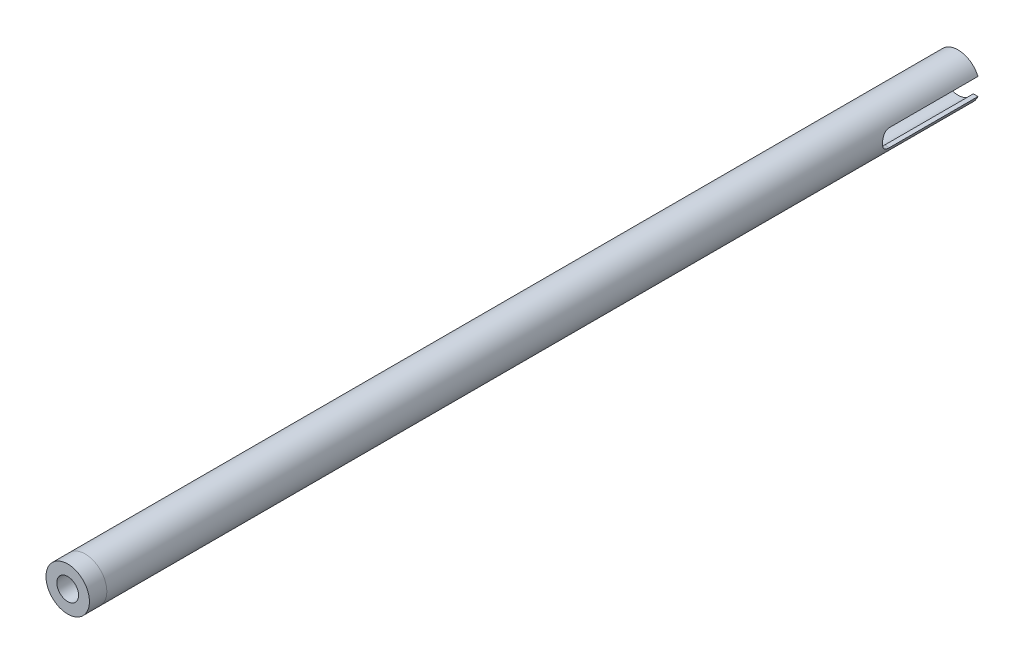
SolidWorks part; units mm, degrees
ref_plane "Front Plane" through (0, 0, 0) normal (0, 0, 1) x (1, 0, 0)
ref_plane "Top Plane" through (0, 0, 0) normal (0, 1, 0) x (1, 0, 0)
ref_plane "Right Plane" through (0, 0, 0) normal (1, 0, 0) x (0, 0, -1)
sketch "Axis" plane through (0, 0, 0) normal (0, 1, 0) x (1, 0, 0)
  line L0 (0, 0) -> (0, 325.114) construction
  line L1 (0, 0) -> (0, -34.925) construction
  line L2 (0, 325.114) -> (-7.9375, 325.114) construction
  line L4 (0, 354.4828) -> (-10.3187, 316.3034) construction
  dimension "D1" = 34.925
  dimension "D2" = 7.9375
sketch "Sketch1" plane through (0, 0, 0) normal (0, 0, 1) x (1, 0, 0)
  line L0 (-7.9375, 0) -> (7.9375, 0) construction
  line L1 (-7.2748, 3.175) -> (7.2748, 3.175)
  line L2 (-7.2748, -3.175) -> (7.2748, -3.175)
  circle A0 centre (0, 0) radius 7.9375
  circle A1 centre (0, 0) radius 6.4135
  circle A2 centre (0, 0) radius 3.9688
  dimension "D1" = 15.875
  dimension "D3" = 7.9375
  dimension "D2" = 1.524
  dimension "D4" = 6.35
extrude "Threaded insert 1-1" add sketch "Sketch1" against normal blind 6.35 contours A2 L1 A1 | A1 L1 A0 | A2 L0 A1 L1 | A1 L0 A0 L1 | L0 A1 L2 A0 | L0 A2 L2 A1 | A2 L2 A1 | A1 L2 A0 | L0 A1 L2 A2 | L0 A0 L2 A1 | A0 L0 A1 L1 | A1 L0 A2 L1 region at (4.7887, 1.6543, 0) region at (4.7887, -1.6543, 0) region at (6.9234, 1.6163, 0) region at (6.9234, -1.6163, 0) region at (-4.7887, -1.6543, 0) region at (-4.7887, 1.6543, 0) region at (0, 4.6159, 0) region at (0, -4.6159, 0) region at (0, 6.5666, 0) region at (6.4237, -3.3281, 0) region at (-6.9234, -1.6163, 0) region at (-6.9234, 1.6163, 0)
extrude "Threaded insert 1-2" add sketch "Sketch1<3>" against normal blind 9.525 from surface contours A2 L1 A1 | A2 L0 A1 L1 | L0 A2 L2 A1 | A2 L2 A1 | L0 A1 L2 A2 | A1 L0 A2 L1 region at (4.7887, 1.6543, 0) region at (4.7887, -1.6543, 0) region at (-4.7887, -1.6543, 0) region at (-4.7887, 1.6543, 0) region at (0, 4.6159, 0) region at (0, -4.6159, 0) starting at face at (7.9375, 0, -6.35)
sketch "Sketch1<3>" plane through (0, 0, 0) normal (0, 0, 1) x (1, 0, 0) same geometry as "Sketch1"
extrude "A-arm tube" add sketch "Sketch1<4>" against normal up to vertex (325.114 mm away) from surface separate body contours A1 L1 A0 | A1 L0 A0 L1 | L0 A1 L2 A0 | A1 L2 A0 | L0 A0 L2 A1 | A0 L0 A1 L1 region at (6.9234, 1.6163, 0) region at (6.9234, -1.6163, 0) region at (0, 6.5666, 0) region at (6.4237, -3.3281, 0) region at (-6.9234, -1.6163, 0) region at (-6.9234, 1.6163, 0) up to point (0, 0, -325.114) starting at face at (6.4135, 0, -6.35)
sketch "Sketch1<4>" plane through (0, 0, 0) normal (0, 0, 1) x (1, 0, 0) same geometry as "Sketch1"
extrude "Apex slot" cut sketch "Sketch1<5>" along normal blind 35.56 from surface contours A0 L0 A1 L1 | L0 A0 L2 A1 | A1 L0 A0 L1 | L0 A1 L2 A0 region at (6.9234, 1.6163, 0) region at (6.9234, -1.6163, 0) region at (-6.9234, -1.6163, 0) region at (-6.9234, 1.6163, 0) starting at face at (6.4135, 0, -325.114)
sketch "Sketch1<5>" plane through (0, 0, 0) normal (0, 0, 1) x (1, 0, 0) same geometry as "Sketch1"
fillet "Fillet1" radius 3.175 4 edges at (-6.4237, 3.175, -289.554) (-6.4237, -3.175, -289.554) (6.4237, -3.175, -289.554) (6.4237, 3.175, -289.554)
equation "\"tube diameter\"= 5 / 8"
equation "\"tube thickness\"= .06"
equation "\"apex thickness\"= .25"
equation "\"tube slot\"= 1.4"
equation "\"D1@Sketch1\"=\"tube diameter\""
equation "\"D2@Sketch1\"=\"tube thickness\""
equation "\"threaded insert hole\"= .3125"
equation "\"D3@Sketch1\"=\"threaded insert hole\""
equation "\"D4@Sketch1\"=\"apex thickness\""
equation "\"D1@Apex slot\" = \"tube slot\""
equation "\"D1@Fillet1\"=\"apex thickness\"/2"
equation "\"D2@Axis\"=\"tube diameter\"/2"
